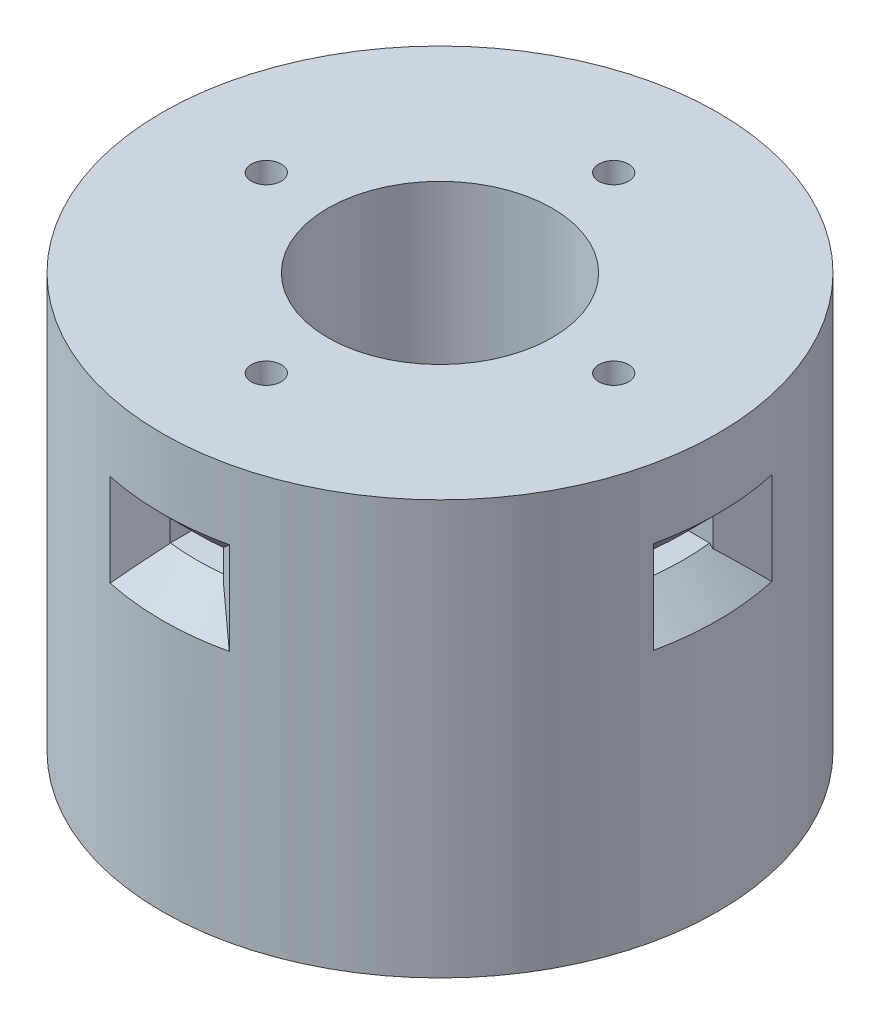
SolidWorks part; units mm, degrees
ref_plane "Front Plane" through (0, 0, 0) normal (0, 0, 1) x (1, 0, 0)
ref_plane "Top Plane" through (0, 0, 0) normal (0, 1, 0) x (1, 0, 0)
ref_plane "Right Plane" through (0, 0, 0) normal (1, 0, 0) x (0, 0, -1)
sketch "Sketch1" plane through (0, 0, 0) normal (0, 1, 0) x (1, 0, 0)
  circle A0 centre (0, 0) radius 40
  dimension "D1" = 80
extrude "Boss-Extrude1" add sketch "Sketch1" along normal blind 10 and the other way blind 49.6
sketch "Sketch2" plane through (0, 10, 0) normal (0, 1, 0) x (1, 0, 0)
  circle A0 centre (0, 0) radius 16.15
  dimension "D1" = 32.3
extrude "Cut-Extrude1" cut sketch "Sketch2" against normal up to next
sketch "Sketch5" plane through (0, 10, 0) normal (0, 1, 0) x (1, 0, 0)
  circle A0 centre (0, 0) radius 25
  circle A1 centre (0, 25) radius 2.15
  circle A2 centre (25, 0) radius 2.15
  circle A3 centre (0, -25) radius 2.15
  circle A4 centre (-25, 0) radius 2.15
  point P14 (0, 0)
  dimension "D1" = 50
  dimension "D2" = 4.3
  dimension "D3" = 4
extrude "m4 heat insert" cut sketch "Sketch5" against normal blind 25 contours A0 A1 | A0 A1 | A0 A2 | A0 A2 | A0 A3 | A0 A4 | A0 A4 | A0 A3
sketch "Sketch6" plane through (0, -49.6, 0) normal (0, -1, 0) x (-1, 0, 0)
  circle A0 centre (0, 0) radius 21.05
  dimension "D1" = 42.1
extrude "Cut-Extrude2" cut sketch "Sketch6" against normal blind 16.5
sketch "Sketch7" plane through (0, 10, 0) normal (0, 1, 0) x (1, 0, 0)
  line L0 (4.0415, 25) -> (4.0415, 39.7953)
  line L1 (4.0415, 25) -> (2.0207, 28.5)
  line L2 (2.0207, 28.5) -> (-2.0207, 28.5)
  line L3 (-2.0207, 28.5) -> (-4.0415, 25)
  line L4 (-4.0415, 25) -> (-2.0207, 21.5)
  line L5 (-2.0207, 21.5) -> (2.0207, 21.5)
  line L6 (2.0207, 21.5) -> (4.0415, 25)
  line L7 (-4.0415, 25) -> (-4.0415, 39.7953)
  circle A0 centre (0, 25) radius 3.5 construction
  circle A1 centre (0, 0) radius 40 construction
  point P1 (3.8101, 39.8181)
  circle M7 centre (0, 25) radius 2.15
  circle M12 centre (0, 0) radius 40
  dimension "D1" = 7
extrude "Cut-Extrude3" cut sketch "Sketch7" against normal blind 3.3 from offset 15 contours L7 L3 L2 L1 L0 M12 | L5 L6 L1 L2 L3 L4 M7 offset against normal yes
pattern_circular "CirPattern1" count 4 over 360 about axis through (0, 0, 0) along (0, 1, 0) of "Cut-Extrude3"
chamfer "Chamfer1" distance 5 angle 45 16 edges at (39.7953, -6.65, 4.0415) (39.7953, -6.65, -4.0415) (40, -5, 0) (40, -8.3, 0) (4.0415, -6.65, 39.7953) (0, -8.3, 40) (0, -5, 40) (-4.0415, -6.65, 39.7953) (-40, -5, 0) (-40, -8.3, 0) (-39.7953, -6.65, -4.0415) (-39.7953, -6.65, 4.0415) (4.0415, -6.65, -39.7953) (-4.0415, -6.65, -39.7953) (0, -5, -40) (0, -8.3, -40)
